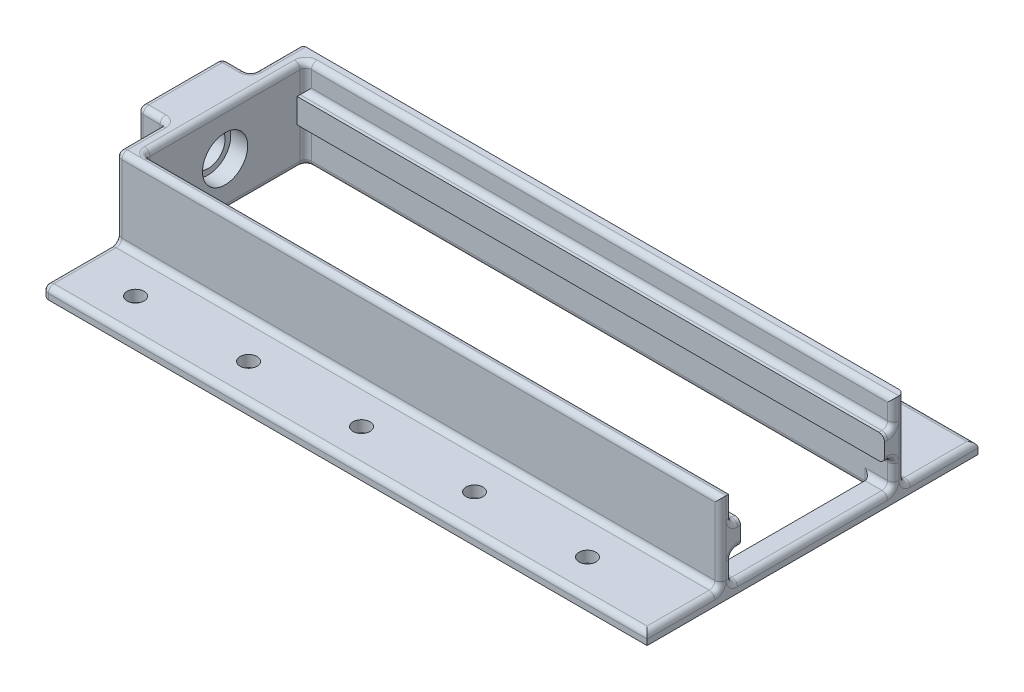
SolidWorks part; units mm, degrees
ref_plane "Front Plane" through (0, 0, 0) normal (0, 0, 1) x (1, 0, 0)
ref_plane "Top Plane" through (0, 0, 0) normal (0, 1, 0) x (1, 0, 0)
ref_plane "Right Plane" through (0, 0, 0) normal (1, 0, 0) x (0, 0, -1)
sketch "Sketch1" plane through (0, 0, 0) normal (0, 1, 0) x (1, 0, 0)
  line L1 (-48.44, 26.4054) -> (58.56, 26.4054)
  line L2 (-48.44, 26.4054) -> (-48.44, -32.1746)
  line L3 (-48.44, -32.1746) -> (58.56, -32.1746)
  line L4 (58.56, 26.4054) -> (58.56, -32.1746)
  dimension "D1" = 58.58
  dimension "D2" = 107
  dimension "D3" = 58.56
extrude "Boss-Extrude1" add sketch "Sketch1" along normal blind 16
sketch "Sketch2" plane through (0, 16, 0) normal (0, 1, 0) x (1, 0, 0)
  line L0 (-48.44, 26.4054) -> (-48.44, -32.1746) construction
  line L1 (-45.44, 11.4054) -> (54.56, 11.4054)
  line L2 (-45.44, 11.4054) -> (-45.44, -17.1746)
  line L3 (-45.44, -17.1746) -> (54.56, -17.1746)
  line L4 (54.56, 11.4054) -> (54.56, -17.1746)
  line L5 (58.56, 26.4054) -> (-48.44, 26.4054) construction
  line L6 (-48.44, -32.1746) -> (58.56, -32.1746) construction
  dimension "D1" = 3
  dimension "D2" = 100
  dimension "D3" = 15
  dimension "D4" = 15
  dimension "D5" = 28.58
extrude "Cut-Extrude1" cut sketch "Sketch2" against normal blind 16
sketch "Sketch3" plane through (0, 16, 0) normal (0, 1, 0) x (1, 0, 0)
  line L0 (58.56, -32.1746) -> (58.56, 26.4054) construction
  line L1 (-48.44, 26.4054) -> (58.56, 26.4054)
  line L2 (-48.44, 26.4054) -> (-48.44, 13.4054)
  line L3 (-48.44, 13.4054) -> (58.56, 13.4054)
  line L4 (58.56, 26.4054) -> (58.56, 13.4054)
  line L5 (-48.44, 26.4054) -> (-48.44, -32.1746) construction
  line L6 (-48.44, -19.1746) -> (58.56, -19.1746)
  line L7 (-48.44, -19.1746) -> (-48.44, -32.1746)
  line L8 (-48.44, -32.1746) -> (58.56, -32.1746)
  line L9 (58.56, -19.1746) -> (58.56, -32.1746)
  line L10 (54.56, 11.4054) -> (-45.44, 11.4054) construction
  line L11 (-45.44, -17.1746) -> (54.56, -17.1746) construction
  line L12 (54.56, -17.1746) -> (54.56, 11.4054) construction
  line L13 (54.56, 11.4054) -> (58.56, 11.4054)
  line L14 (54.56, 11.4054) -> (54.56, -17.1746)
  line L15 (54.56, -17.1746) -> (58.56, -17.1746)
  line L16 (58.56, 11.4054) -> (58.56, -17.1746)
  dimension "D1" = 2
  dimension "D2" = 2
  dimension "D3" = 0
  dimension "D4" = 2
  dimension "D5" = 2
extrude "Cut-Extrude2" cut sketch "Sketch3" against normal blind 14
sketch "Sketch4" plane through (-48.44, 0, 0) normal (-1, 0, 0) x (0, 0, 1)
  line L6 (-26.4054, 0) -> (32.1746, 0) construction
  line L7 (-4.6154, 16) -> (10.3846, 16)
  line L8 (-4.6154, 16) -> (-4.6154, 0)
  line L9 (-4.6154, 0) -> (10.3846, 0)
  line L10 (10.3846, 16) -> (10.3846, 0)
  line L11 (-13.4054, 16) -> (19.1746, 16) construction
  circle A0 centre (2.8846, 8) radius 3
  point P8 (2.8846, 16)
  point P9 (2.8846, 16)
  dimension "D2" = 6
  dimension "D1" = 15
extrude "Boss-Extrude2" add sketch "Sketch4" along normal blind 5
sketch "Sketch6" plane through (0, 0, 17.1746) normal (0, 0, -1) x (-1, 0, 0)
  line L0 (-58.56, 9) -> (71.9078, 9) construction
  line L1 (-58.56, 2) -> (-58.56, 16) construction
  line L2 (48.44, 2) -> (48.44, 16) construction
  line L3 (-58.56, 11.18) -> (48.44, 11.18)
  line L4 (-58.56, 11.18) -> (-58.56, 6.82)
  line L5 (-58.56, 6.82) -> (48.44, 6.82)
  line L6 (48.44, 11.18) -> (48.44, 6.82)
  point P10 (48.44, 9)
  dimension "D1" = 4.36
extrude "Boss-Extrude3" add sketch "Sketch6" along normal blind 1.54
pattern_linear "LPattern1" count 2 spacing 27.04 along (0, 0, -1) of "Boss-Extrude3"
fillet "Fillet1" radius 1 58 edges at (58.56, 6.82, -10.6354) (-45.44, 16, 2.8846) (58.56, 11.18, -10.6354) (-45.44, 0, 2.8846) (54.56, 0, 2.8846) (58.56, 2, 2.8846) (58.56, 6.82, 16.4046) (58.56, 4.41, -11.4054) (56.56, 2, -11.4054) (54.56, 1, -11.4054) (4.56, 0, -11.4054) (-45.44, 3.41, -11.4054) (6.56, 6.82, -11.4054) (-45.44, 13.59, -11.4054) (6.56, 16, -11.4054) (58.56, 13.59, -11.4054) (6.56, 11.18, -11.4054) (-45.44, 3.41, 17.1746) (4.56, 0, 17.1746) (54.56, 1, 17.1746) (56.56, 2, 17.1746) (58.56, 4.41, 17.1746) (6.56, 6.82, 17.1746) (5.06, 2, 19.1746) (58.56, 11.18, 16.4046) (-50.94, 16, 10.3846) (-50.94, 0, 10.3846) (-50.94, 0, -4.6154) (-50.94, 16, -4.6154) (58.56, 9, -13.4054) (58.56, 9, 19.1746) (5.06, 16, 19.1746) (58.56, 2, 25.6746) (5.06, 2, 32.1746) (58.56, 13.59, 17.1746) (6.56, 16, 17.1746) (-45.44, 13.59, 17.1746) (6.56, 11.18, 17.1746) (-48.44, 16, 14.7796) (-48.44, 9, 19.1746) (-48.44, 2, 25.6746) (-48.44, 1, 32.1746) (-48.44, 0, 21.2796) (-48.44, 8, 10.3846) (-53.44, 8, 5.8846) (-53.44, 16, 2.8846) (-53.44, 8, 10.3846) (-53.44, 0, 2.8846) (-53.44, 8, -4.6154) (-48.44, 0, -15.5104) (-48.44, 1, -26.4054) (-48.44, 9, -13.4054) (-48.44, 16, -9.0104) (-48.44, 8, -4.6154) (5.06, 2, -26.4054) (58.56, 2, -19.9054) (5.06, 2, -13.4054) (-48.44, 2, -19.9054)
sketch "Sketch8" plane through (-48.44, 0, 0) normal (-1, 0, 0) x (0, 0, 1)
  circle A0 centre (2.8846, 8) radius 4
extrude "Cut-Extrude3" cut sketch "Sketch8" against normal blind 5
sketch "Sketch9" plane through (0, 2, 0) normal (0, 1, 0) x (1, 0, 0)
  line L0 (-38.2951, 20.1064) -> (-18.2951, 20.1064) construction
  line L2 (-52.44, -2.8846) -> (62.9221, -2.8846) construction
  line L3 (-52.44, 3.6154) -> (-52.44, -9.3846) construction
  circle A0 centre (-38.2951, 20.1064) radius 1.5
  circle A1 centre (-18.2951, 20.1064) radius 1.5
  circle A2 centre (1.7049, 20.1064) radius 1.5
  circle A3 centre (21.7049, 20.1064) radius 1.5
  circle A4 centre (41.7049, 20.1064) radius 1.5
  circle A5 centre (41.7049, -25.8756) radius 1.5
  circle A6 centre (21.7049, -25.8756) radius 1.5
  circle A7 centre (1.7049, -25.8756) radius 1.5
  circle A8 centre (-18.2951, -25.8756) radius 1.5
  circle A9 centre (-38.2951, -25.8756) radius 1.5
  dimension "D1" = 3
  dimension "D3" = 20
  dimension "D2" = 5
extrude "Cut-Extrude4" cut sketch "Sketch9" against normal through all both and the other way through all
